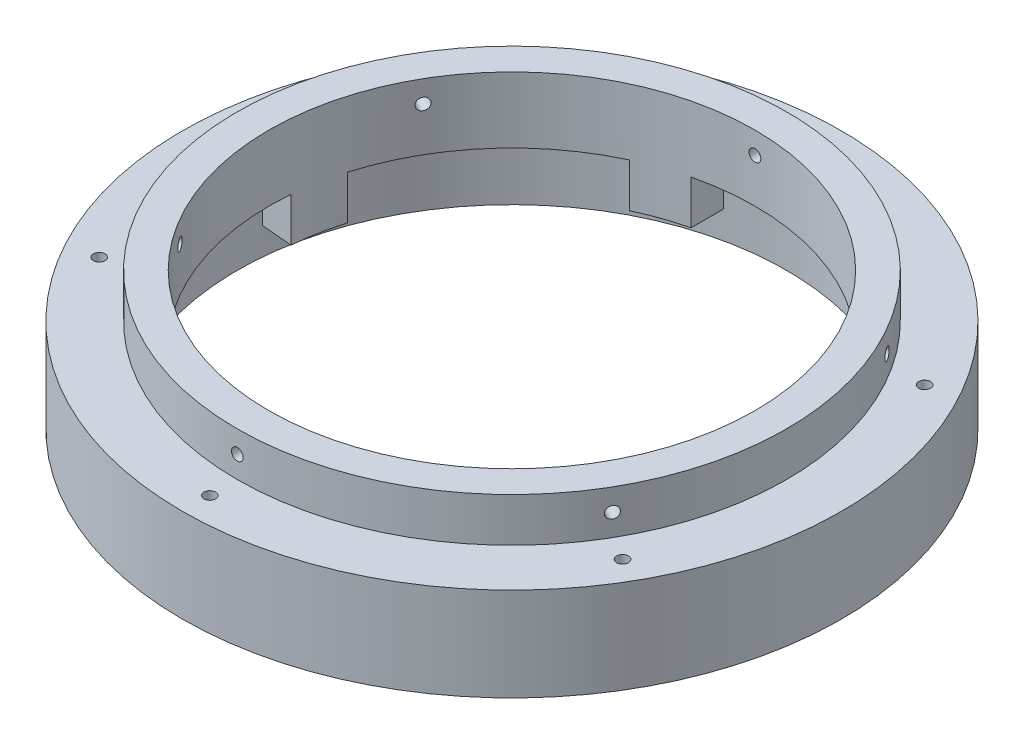
SolidWorks part; units mm, degrees
ref_plane "Front Plane" through (0, 0, 0) normal (0, 0, 1) x (1, 0, 0)
ref_plane "Top Plane" through (0, 0, 0) normal (0, 1, 0) x (1, 0, 0)
ref_plane "Right Plane" through (0, 0, 0) normal (1, 0, 0) x (0, 0, -1)
sketch "Sketch1" plane through (0, 0, 0) normal (0, 1, 0) x (1, 0, 0)
  circle A0 centre (0, 0) radius 63.5
  circle A1 centre (0, 0) radius 76.2
  circle A2 centre (0, 0) radius 56.1975
  dimension "D1" = 152.4
  dimension "D3" = 112.395
  dimension "D2" = 12.7
extrude "Boss-Extrude1" add sketch "Sketch1" along normal blind 15.24 contours A0 A2 region at (-61.7039, 0, 0)
extrude "Boss-Extrude2" add sketch "Sketch1<4>" along normal blind 5.08 and the other way blind 16.51 contours A1 A0 region at (-74.0447, 0, 0)
sketch "Sketch1<4>" plane through (0, 0, 0) normal (0, 1, 0) x (1, 0, 0) same geometry as "Sketch1"
sketch "Sketch3" plane through (0, -16.51, 0) normal (0, -1, 0) x (1, 0, 0)
  line L0 (0, 0) -> (-68.319, 5.9771) construction
  line L1 (0, 0) -> (0, 69.85) construction
  line L2 (0, 0) -> (48.9804, 58.3726)
  line L3 (0, 0) -> (13.232, 75.0424)
  line L4 (-13.2113, -54.6225) -> (-13.2113, -60.147)
  line L5 (13.2113, -54.6225) -> (13.2113, -60.147)
  line L6 (-13.2113, -60.147) -> (13.2113, -60.147)
  line L7 (-13.2113, -60.147) -> (-13.2113, -62.1105)
  line L8 (-23.7501, -50.9322) -> (-26.8363, -57.5505)
  line L9 (0, 0) -> (-23.7501, -50.9322) construction
  circle A0 centre (-68.319, 5.9771) radius 3.9561
  circle A1 centre (0, 69.85) radius 1.3589
  circle A2 centre (0, 0) radius 76.2 construction
  circle A5 centre (0, 0) radius 56.1975 construction
  circle A6 centre (0, 0) radius 63.5 construction
  arc A7 (-26.8363, -57.5505) -> (-13.2113, -62.1105) centre (0, 0) ccw
  arc A9 (-23.7501, -50.9322) -> (-13.2113, -54.6225) centre (0, 0) ccw
  point P0 (0, -60.147)
  dimension "D4" = 7.9121
  dimension "D5" = 2.7178
  dimension "D2" = 85
  dimension "D3" = 69.85
  dimension "D6" = 30
  dimension "D7" = 10
  dimension "D9" = 26.4227
  dimension "D8" = 5.5245
  dimension "D10" = 25
extrude "Cut-Extrude1" cut sketch "Sketch3" against normal blind 15.24 contours A0
extrude "Cut-Extrude2" cut sketch "Sketch3<3>" against normal through all contours A1 | A1 region at (0, -16.51, 69.85)
sketch "Sketch3<3>" plane through (0, -16.51, 0) normal (0, -1, 0) x (1, 0, 0) same geometry as "Sketch3"
pattern_circular "CirPattern1" count 3 over 360 about axis through (0, -16.51, 0) along (0, 1, 0) of "Cut-Extrude1"
pattern_circular "CirPattern2" count 6 over 360 about axis through (0, -16.51, 0) along (0, 1, 0) of "Cut-Extrude2"
ref_plane "Plane1" through (0, 0, 76.2) normal (0, 0, 1) x (1, 0, 0)
sketch "Sketch5" plane through (0, 0, 76.2) normal (0, 0, 1) x (1, 0, 0)
  line L0 (0, -16.51) -> (0, 10.16) construction
  line L1 (-1.3589, -16.51) -> (1.3589, -16.51) construction
  circle A0 centre (0, 10.16) radius 1.3589
  dimension "D2" = 2.7178
  dimension "D1" = 26.67
extrude "Cut-Extrude3" cut sketch "Sketch5" against normal up to surface (132.3811 mm away) up to face at (0, 15.24, 56.1975)
extrude "Boss-Extrude3" add sketch "Sketch3<11>" along normal blind 10.16 from surface contours L4 A9 L8 A7 L7 starting at face at (0, 0, 56.1975)
sketch "Sketch3<11>" plane through (0, -16.51, 0) normal (0, -1, 0) x (1, 0, 0) same geometry as "Sketch3"
pattern_circular "CirPattern3" count 6 over 360 about axis through (0, 15.24, 0) along (0, 1, 0) of "Cut-Extrude3", "Boss-Extrude3"
equation "\"Middle Coupler Inner Daimeter\"= 3.875in"
equation "\"Middle Coupler  Wall Thickness\"= 0.25in"
equation "\"Middle Coupler Bottom Thickness\"= 0.2in"
equation "\"Bearing Rail Offset\"= 0.45in"
equation "\"3-56 UNF Tap\"= 0.089in"
equation "\"3-48 Tap\"= 0.079in"
equation "\"3-56 UNF Clearance\"= 0.104in"
equation "\"3-48 Clearance\"= 0.104in"
equation "\"Ball Bearing Distance\"= 0.03in"
equation "\"TCA Outer Diameter\"= 6in"
equation "\"Interstage Aeroframe Wall Thickness\"= 0.072in"
equation "\"Compression Spring OD\"= 0.42in"
equation "\"10-24 Tap\"= 0.157in"
equation "\"10-24 Clearance\"= 0.196in"
equation "\"Lower Stage Fuselage Wall Thickness\"= 0.25in"
equation "\"6-32 Tap\"= 0.107in"
equation "\"6-32 Clearance\"= 0.144"
equation "\"1/4-20 Tap\"= 0.201in"
equation "\"12-24 Tap\"= 0.177in"
equation "\"D1@Sketch1\"=\"TCA Outer Diameter\""
equation "\"D5@Sketch3\"=\"6-32 Tap\""
equation "\"D1@Sketch5\"=\"D2@Boss-Extrude2\"+(\"D1@Boss-Extrude2\"+\"D1@Boss-Extrude1\")/2"
equation "\"D2@Sketch5\"=\"6-32 Tap\""
equation "\"D8@Sketch3\"=3/16+0.03"
equation "\"D3@Sketch1\"=\"Middle Coupler Inner Daimeter\" + 0.55"
